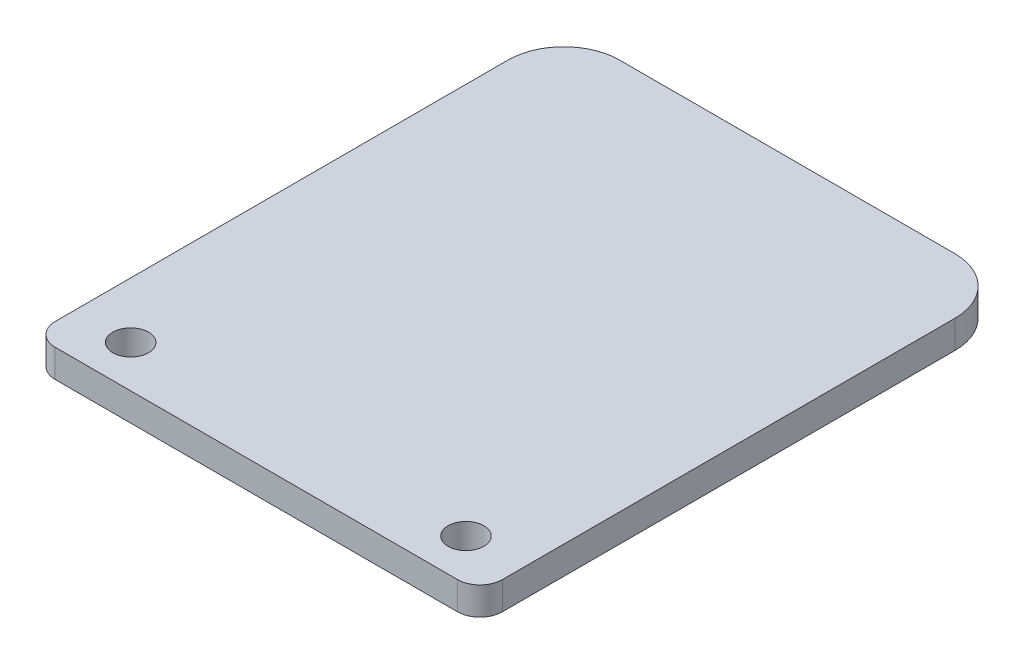
SolidWorks part; units mm, degrees
ref_plane "Front Plane" through (0, 0, 0) normal (0, 0, 1) x (1, 0, 0)
ref_plane "Top Plane" through (0, 0, 0) normal (0, 1, 0) x (1, 0, 0)
ref_plane "Right Plane" through (0, 0, 0) normal (1, 0, 0) x (0, 0, -1)
sketch "Sketch1" plane through (0, 0, 0) normal (0, 1, 0) x (1, 0, 0)
  line L1 (-25.4, 30.1625) -> (25.4, 30.1625)
  line L2 (-25.4, 30.1625) -> (-25.4, -30.1625)
  line L3 (-25.4, -30.1625) -> (25.4, -30.1625)
  line L4 (25.4, 30.1625) -> (25.4, -30.1625)
  line L5 (-25.4, 30.1625) -> (25.4, -30.1625) construction
  line L6 (-25.4, -30.1625) -> (25.4, 30.1625) construction
  point P0 (0, 0)
  dimension "D1" = 50.8
  dimension "D2" = 60.325
extrude "Boss-Extrude1" add sketch "Sketch1" along normal blind 3.175
sketch "Sketch2" plane through (0, 0, 0) normal (0, -1, 0) x (-1, 0, 0)
  line L0 (25.4, -30.1625) -> (-25.4, -30.1625) construction
  line L1 (-19.05, -25.4) -> (-25.4, -25.4) construction
  line L2 (-25.4, -30.1625) -> (-25.4, 30.1625) construction
  line L3 (19.05, -25.4) -> (25.4, -25.4) construction
  line L4 (25.4, 30.1625) -> (25.4, -30.1625) construction
  circle A0 centre (-19.05, -25.4) radius 2.032
  circle A1 centre (19.05, -25.4) radius 2.032
  dimension "D2" = 4.064
  dimension "D1" = 4.7625
  dimension "D3" = 38.1
extrude "Cut-Extrude1" cut sketch "Sketch2" against normal through all
fillet "Fillet1" radius 2.54 2 edges at (-25.4, 1.5875, 30.1625) (25.4, 1.5875, 30.1625)
fillet "Fillet2" radius 6.35 2 edges at (25.4, 1.5875, -30.1625) (-25.4, 1.5875, -30.1625)
